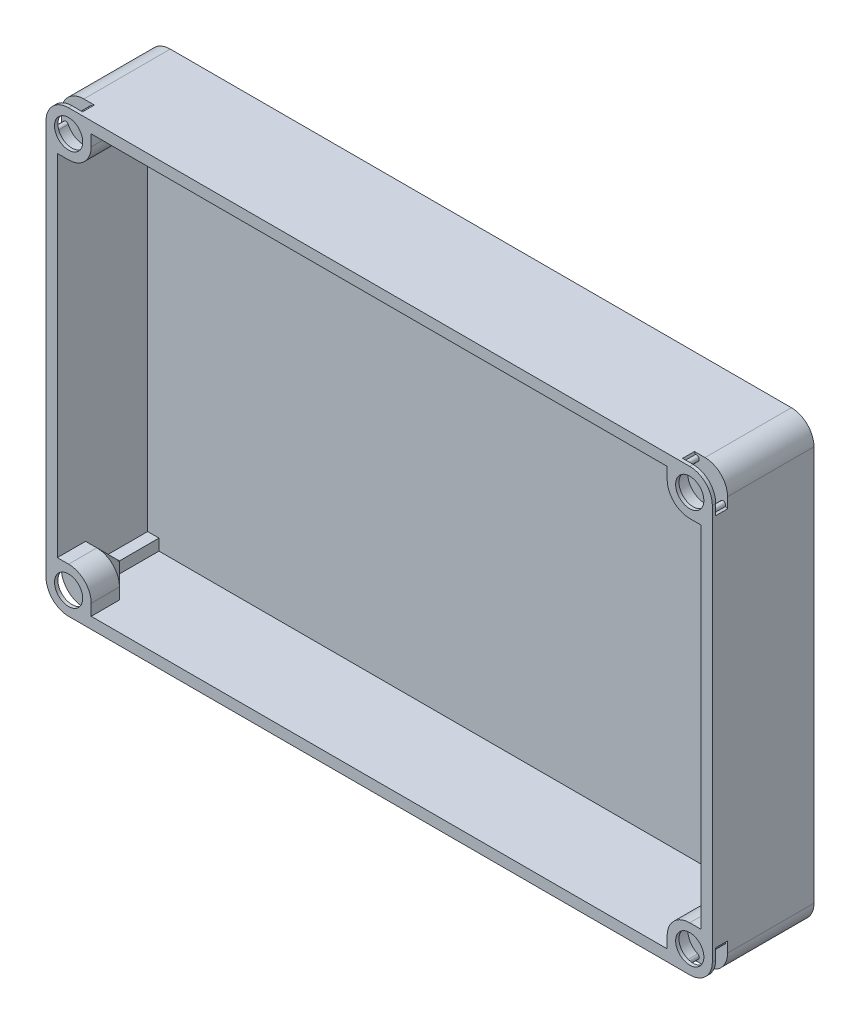
SolidWorks part; units mm, degrees
ref_plane "前视基准面" through (0, 0, 0) normal (0, 0, 1) x (1, 0, 0)
ref_plane "上视基准面" through (0, 0, 0) normal (0, 1, 0) x (1, 0, 0)
ref_plane "右视基准面" through (0, 0, 0) normal (1, 0, 0) x (0, 0, -1)
sketch "草图1" plane through (0, 0, 0) normal (0, 0, 1) x (1, 0, 0)
  line L1 (-59, -39) -> (59, -39)
  line L2 (-59, -39) -> (-59, 39)
  line L3 (-59, 39) -> (59, 39)
  line L4 (59, -39) -> (59, 39)
  line L5 (-59, -39) -> (59, 39) construction
  line L6 (-59, 39) -> (59, -39) construction
  point P0 (0, 0)
  dimension "D1" = 118
  dimension "D2" = 78
extrude "凸台-拉伸1" add sketch "草图1" along normal blind 2
fillet "圆角1" radius 4 4 edges at (59, 39, 1) (59, -39, 1) (-59, -39, 1) (-59, 39, 1)
sketch "草图4" plane through (0, 0, 2) normal (0, 0, 1) x (1, 0, 0)
  line L0 (57, -35) -> (57, 35)
  line L1 (55, 37) -> (-55, 37)
  line L2 (-57, 35) -> (-57, -35)
  line L3 (-55, -37) -> (55, -37)
  line L4 (59, -35) -> (59, 35)
  line L5 (55, 39) -> (-55, 39)
  line L6 (-59, 35) -> (-59, -35)
  line L7 (-55, -39) -> (55, -39)
  line L8 (59, -35) -> (59, 35)
  line L9 (55, 39) -> (-55, 39)
  line L10 (-59, 35) -> (-59, -35)
  line L11 (-55, -39) -> (55, -39)
  arc A0 (57, 35) -> (55, 37) centre (55, 35) ccw
  arc A1 (-55, 37) -> (-57, 35) centre (-55, 35) ccw
  arc A2 (-57, -35) -> (-55, -37) centre (-55, -35) ccw
  arc A3 (55, -37) -> (57, -35) centre (55, -35) ccw
  arc A4 (59, 35) -> (55, 39) centre (55, 35) ccw
  arc A5 (-55, 39) -> (-59, 35) centre (-55, 35) ccw
  arc A6 (-59, -35) -> (-55, -39) centre (-55, -35) ccw
  arc A7 (55, -39) -> (59, -35) centre (55, -35) ccw
  arc A8 (59, 35) -> (55, 39) centre (55, 35) ccw
  arc A9 (-55, 39) -> (-59, 35) centre (-55, 35) ccw
  arc A10 (-59, -35) -> (-55, -39) centre (-55, -35) ccw
  arc A11 (55, -39) -> (59, -35) centre (55, -35) ccw
  dimension "D1" = 0
  dimension "D2" = 2
extrude "凸台-拉伸4" add sketch "草图4" along normal blind 16
sketch "草图5" plane through (0, 0, 18) normal (0, 0, 1) x (1, 0, 0)
  line L0 (-51, 35) -> (-51, 39)
  line L1 (55, 39) -> (-55, 39) construction
  line L2 (-55, 31) -> (-59, 31)
  line L3 (-59, 35) -> (-59, -35) construction
  line L4 (-59, 31) -> (-59, 35)
  line L5 (-51, 39) -> (-55, 39)
  line L6 (0, 46.3045) -> (0, -48.7609) construction
  line L7 (-64.9291, 0) -> (64.4047, 0) construction
  line L8 (51, 39) -> (55, 39)
  line L9 (59, 31) -> (59, 35)
  line L10 (55, 31) -> (59, 31)
  line L11 (51, 35) -> (51, 39)
  line L12 (51, -35) -> (51, -39)
  line L13 (55, -31) -> (59, -31)
  line L14 (59, -31) -> (59, -35)
  line L15 (51, -39) -> (55, -39)
  line L16 (-51, -39) -> (-55, -39)
  line L17 (-59, -31) -> (-59, -35)
  line L18 (-55, -31) -> (-59, -31)
  line L19 (-51, -35) -> (-51, -39)
  arc A2 (-55, 31) -> (-51, 35) centre (-55, 35) ccw
  arc A4 (-55, 39) -> (-59, 35) centre (-55, 35) ccw construction
  arc A5 (-55, 39) -> (-59, 35) centre (-55, 35) ccw
  arc A6 (55, 39) -> (59, 35) centre (55, 35) cw
  arc A7 (55, 31) -> (51, 35) centre (55, 35) cw
  arc A8 (55, -31) -> (51, -35) centre (55, -35) ccw
  arc A9 (55, -39) -> (59, -35) centre (55, -35) ccw
  arc A10 (-55, -39) -> (-59, -35) centre (-55, -35) cw
  arc A11 (-55, -31) -> (-51, -35) centre (-55, -35) cw
extrude "凸台-拉伸5" add sketch "草图5" against normal blind 9
sketch "草图6" plane through (0, 0, 18) normal (0, 0, 1) x (1, 0, 0)
  line L0 (-63.6672, 0) -> (65.0609, 0) construction
  line L1 (0, 48.0412) -> (0, -51.6033) construction
  circle A0 centre (-55, 35) radius 2.5
  circle A1 centre (55, 35) radius 2.5
  circle A2 centre (55, -35) radius 2.5
  circle A3 centre (-55, -35) radius 2.5
  dimension "D1" = 5
extrude "切除-拉伸1" cut sketch "草图6" against normal blind 0.6
sketch "草图7" plane through (0, 0, 17.4) normal (0, 0, 1) x (1, 0, 0)
  line L0 (55, 35) -> (57.8225, 37.8225) construction
  line L1 (55, 35) -> (56.2811, 35) construction
  line L2 (53.5103, 38.1947) -> (55, 35) construction
  line L3 (53.3095, 38.6252) -> (52.8869, 39.5315)
  line L4 (58.6252, 33.3095) -> (59.5315, 32.8869)
  line L5 (-64.866, 0) -> (45.0874, 0) construction
  line L6 (0, 48.8603) -> (0, -53.3734) construction
  line L7 (-53.5103, 38.1947) -> (-55, 35) construction
  line L8 (-55, 35) -> (-56.2811, 35) construction
  line L9 (-55, 35) -> (-57.8225, 37.8225) construction
  line L10 (-58.6252, 33.3095) -> (-59.5315, 32.8869)
  line L11 (-53.3095, 38.6252) -> (-52.8869, 39.5315)
  line L12 (53.5103, -38.1947) -> (55, -35) construction
  line L13 (55, -35) -> (56.2811, -35) construction
  line L14 (55, -35) -> (57.8225, -37.8225) construction
  line L15 (58.6252, -33.3095) -> (59.5315, -32.8869)
  line L16 (53.3095, -38.6252) -> (52.8869, -39.5315)
  line L17 (-55, -35) -> (-57.8225, -37.8225) construction
  line L18 (-55, -35) -> (-56.2811, -35) construction
  line L19 (-53.5103, -38.1947) -> (-55, -35) construction
  line L20 (-53.3095, -38.6252) -> (-52.8869, -39.5315)
  line L21 (-58.6252, -33.3095) -> (-59.5315, -32.8869)
  arc A0 (53.711, 37.7642) -> (57.7642, 33.711) centre (55, 35) ccw
  arc A1 (53.711, 37.7642) -> (53.3095, 38.6252) centre (53.5103, 38.1947) ccw
  arc A2 (57.7642, 33.711) -> (58.6252, 33.3095) centre (58.1947, 33.5103) cw
  circle A3 centre (55, 35) radius 4 construction
  arc A4 (59.5315, 32.8869) -> (52.8869, 39.5315) centre (55, 35) ccw
  circle A5 centre (-55, 35) radius 4 construction
  arc A6 (-59.5315, 32.8869) -> (-52.8869, 39.5315) centre (-55, 35) cw
  arc A7 (-57.7642, 33.711) -> (-58.6252, 33.3095) centre (-58.1947, 33.5103) ccw
  arc A8 (-53.711, 37.7642) -> (-53.3095, 38.6252) centre (-53.5103, 38.1947) cw
  arc A9 (-53.711, 37.7642) -> (-57.7642, 33.711) centre (-55, 35) cw
  circle A10 centre (55, -35) radius 4 construction
  arc A11 (59.5315, -32.8869) -> (52.8869, -39.5315) centre (55, -35) cw
  arc A12 (57.7642, -33.711) -> (58.6252, -33.3095) centre (58.1947, -33.5103) ccw
  arc A13 (53.711, -37.7642) -> (53.3095, -38.6252) centre (53.5103, -38.1947) cw
  arc A14 (53.711, -37.7642) -> (57.7642, -33.711) centre (55, -35) cw
  circle A15 centre (-55, -35) radius 4 construction
  arc A16 (-53.711, -37.7642) -> (-57.7642, -33.711) centre (-55, -35) ccw
  arc A17 (-53.711, -37.7642) -> (-53.3095, -38.6252) centre (-53.5103, -38.1947) ccw
  arc A18 (-57.7642, -33.711) -> (-58.6252, -33.3095) centre (-58.1947, -33.5103) cw
  arc A19 (-59.5315, -32.8869) -> (-52.8869, -39.5315) centre (-55, -35) ccw
  dimension "D1" = 6.1
  dimension "D4" = 10
  dimension "D2" = 45
  dimension "D3" = 70
extrude "切除-拉伸2" cut sketch "草图7" against normal blind 2.1
chamfer "倒角1" distance 4 angle 45 12 edges at (-56, 31, 9) (-51, 36, 9) (-52.1716, 32.1716, 9) (51, 36, 9) (56, 31, 9) (52.1716, 32.1716, 9) (56, -31, 9) (51, -36, 9) (52.1716, -32.1716, 9) (-56, -31, 9) (-51, -36, 9) (-52.1716, -32.1716, 9)
sketch "草图8" plane through (0, 0, 9) normal (0, 0, -1) x (-1, 0, 0)
  line L0 (-55, -37) -> (-55, -35) construction
  line L1 (-55, -35) -> (-57, -35) construction
  line L2 (57, -35) -> (55, -35) construction
  line L3 (55, -35) -> (55, -37) construction
  line L4 (55, 37) -> (55, 35) construction
  line L5 (55, 35) -> (57, 35) construction
  line L6 (-57, 35) -> (-55, 35) construction
  line L7 (-55, 35) -> (-55, 37) construction
  line L8 (-55, -37) -> (-55, -35)
  line L9 (-55, -35) -> (-57, -35)
  line L10 (57, -35) -> (55, -35)
  line L11 (55, -35) -> (55, -37)
  line L12 (55, 37) -> (55, 35)
  line L13 (55, 35) -> (57, 35)
  line L14 (-57, 35) -> (-55, 35)
  line L15 (-55, 35) -> (-55, 37)
  arc A0 (-57, -35) -> (-55, -37) centre (-55, -35) ccw construction
  arc A1 (55, -37) -> (57, -35) centre (55, -35) ccw construction
  arc A2 (57, 35) -> (55, 37) centre (55, 35) ccw construction
  arc A3 (-55, 37) -> (-57, 35) centre (-55, 35) ccw construction
  arc A4 (-57, -35) -> (-55, -37) centre (-55, -35) ccw
  arc A5 (55, -37) -> (57, -35) centre (55, -35) ccw
  arc A6 (57, 35) -> (55, 37) centre (55, 35) ccw
  arc A7 (-55, 37) -> (-57, 35) centre (-55, 35) ccw
extrude "凸台-拉伸6" add sketch "草图8" along normal up to surface (7 mm away) up to face at (0, 0, 2)
